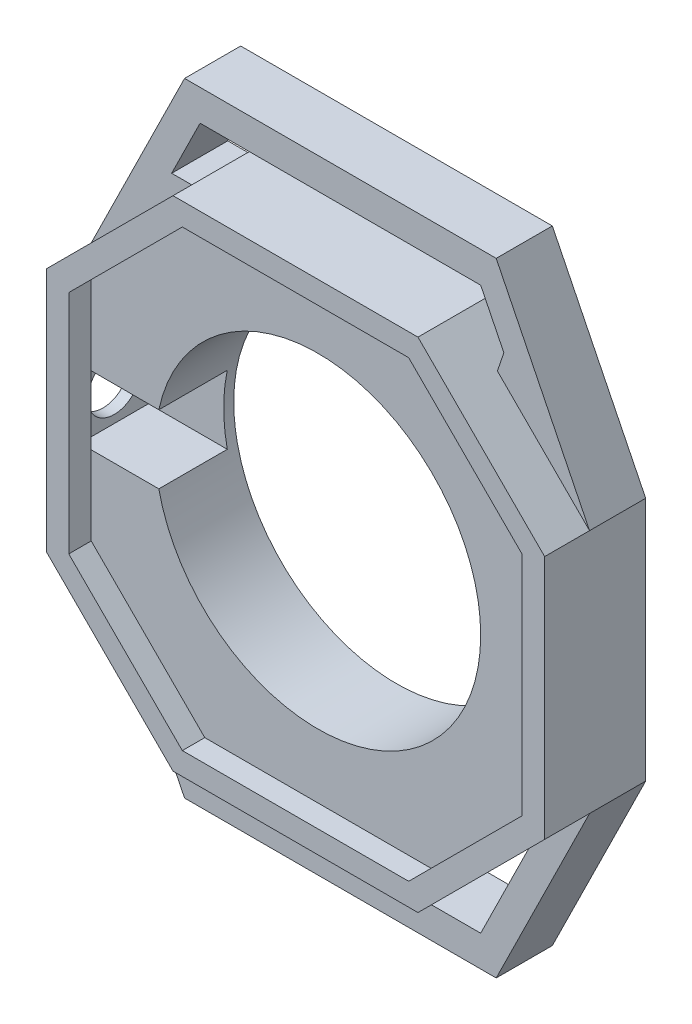
SolidWorks part; units mm, degrees
ref_plane "Front Plane" through (0, 0, 0) normal (0, 0, 1) x (1, 0, 0)
ref_plane "Top Plane" through (0, 0, 0) normal (0, 1, 0) x (1, 0, 0)
ref_plane "Right Plane" through (0, 0, 0) normal (1, 0, 0) x (0, 0, -1)
ref_plane "Plane1" through (0, 0, 0) normal (0, 0, -1) x (-1, 0, 0)
sketch "Sketch1" plane through (0, 0, 0) normal (0, 0, -1) x (-1, 0, 0)
  line L0 (-144.96, -75.66) -> (-164.96, -75.66) construction
  line L1 (-134.96, -85.66) -> (-144.96, -75.66) construction
  line L2 (-134.96, -105.66) -> (-134.96, -85.66) construction
  line L3 (-144.96, -115.66) -> (-134.96, -105.66) construction
  line L4 (-164.96, -115.66) -> (-144.96, -115.66) construction
  line L5 (-174.96, -105.66) -> (-164.96, -115.66) construction
  line L6 (-174.96, -85.66) -> (-174.96, -105.66) construction
  line L7 (-164.96, -75.66) -> (-174.96, -85.66) construction
  line L8 (-144.96, -75.66) -> (-164.96, -75.66) construction
  line L9 (-134.96, -85.66) -> (-144.96, -75.66) construction
  line L10 (-134.96, -105.66) -> (-134.96, -85.66) construction
  line L11 (-144.96, -115.66) -> (-134.96, -105.66) construction
  line L12 (-164.96, -115.66) -> (-144.96, -115.66) construction
  line L13 (-174.96, -105.66) -> (-164.96, -115.66) construction
  line L14 (-174.96, -85.66) -> (-174.96, -105.66) construction
  line L15 (-164.96, -75.66) -> (-174.96, -85.66) construction
  line L16 (-144.8772, -75.46) -> (-165.0428, -75.46)
  line L17 (-165.0428, -75.46) -> (-175.16, -85.5772)
  line L18 (-175.16, -85.5772) -> (-175.16, -105.7428)
  line L19 (-175.16, -105.7428) -> (-165.0428, -115.86)
  line L20 (-165.0428, -115.86) -> (-144.8772, -115.86)
  line L21 (-144.8772, -115.86) -> (-134.76, -105.7428)
  line L22 (-134.76, -105.7428) -> (-134.76, -85.5772)
  line L23 (-134.76, -85.5772) -> (-144.8772, -75.46)
  line L24 (-132.76, -106.5713) -> (-132.76, -84.7487)
  line L25 (-132.76, -84.7487) -> (-144.0487, -73.46)
  line L26 (-144.0487, -73.46) -> (-165.8713, -73.46)
  line L27 (-165.8713, -73.46) -> (-177.16, -84.7487)
  line L28 (-177.16, -84.7487) -> (-177.16, -106.5713)
  line L29 (-177.16, -106.5713) -> (-165.8713, -117.86)
  line L30 (-165.8713, -117.86) -> (-144.0487, -117.86)
  line L31 (-144.0487, -117.86) -> (-132.76, -106.5713)
  circle A0 centre (-154.96, -95.66) radius 13.5 construction
  circle A1 centre (-154.96, -95.66) radius 13.5 construction
  circle A2 centre (-154.96, -95.66) radius 14.5
  dimension "D1" = 1
  dimension "D2" = 0.2
  dimension "D3" = 2
extrude "Boss-Extrude1" add sketch "Sketch1" along normal blind 7 contours A2 | L27 L28 L29 L30 L31 L24 L25 L26 region at (154.96, -95.66, 0)
extrude "Boss-Extrude2" add sketch "Sketch1<3>" against normal blind 2 contours L30 L31 L24 L25 L26 L27 L28 L29 L23 L22 L21 L20 L19 L18 L17 L16 region at (138.8484, -111.7716, 0)
sketch "Sketch1<3>" plane through (0, 0, 0) normal (0, 0, -1) x (-1, 0, 0) same geometry as "Sketch1"
ref_plane "Plane2" through (0, 0, -3.5) normal (0, 0, 1) x (1, 0, 0)
sketch "Sketch2" plane through (0, 0, -7) normal (0, 0, 1) x (1, 0, 0)
  line L0 (142.46, -70.66) -> (167.46, -70.66)
  line L1 (141.078, -70.66) -> (141.078, -67.896) construction
  line L2 (168.842, -70.66) -> (168.842, -67.896) construction
  line L3 (141.078, -67.896) -> (168.842, -67.896)
  line L4 (144.0487, -73.46) -> (165.8713, -73.46) construction
  line L5 (154.96, -73.46) -> (154.96, -68.7069) construction
  line L6 (132.76, -84.7487) -> (141.078, -67.896)
  line L7 (168.842, -70.66) -> (168.842, -73.46) construction
  line L9 (144.0487, -73.46) -> (141.078, -73.46) construction
  line L10 (141.078, -73.46) -> (141.078, -70.66) construction
  line L11 (168.842, -70.66) -> (168.842, -73.46) construction
  line L12 (168.842, -73.46) -> (165.8713, -73.46) construction
  line L13 (177.16, -84.7487) -> (168.842, -67.896)
  line L15 (141.078, -70.66) -> (141.078, -73.46) construction
  line L17 (138.1827, -79.326) -> (132.76, -84.7487)
  line L18 (171.7373, -79.326) -> (177.16, -84.7487)
  line L19 (141.078, -73.46) -> (138.1827, -79.326)
  line L20 (168.842, -73.46) -> (171.7373, -79.326)
  line L21 (144.0487, -73.46) -> (138.1827, -79.326) construction
  line L22 (165.8713, -73.46) -> (171.7373, -79.326) construction
  line L23 (141.078, -73.46) -> (142.46, -70.66)
  line L24 (168.842, -73.46) -> (167.46, -70.66)
  line L25 (141.078, -70.66) -> (142.46, -70.66) construction
  line L26 (167.46, -70.66) -> (168.842, -70.66) construction
  line L27 (154.96, -95.66) -> (141.078, -67.896) construction
  point P22 (0, 0)
  line M19 (165.8713, -73.46) -> (177.16, -84.7487)
  line M25 (132.76, -84.7487) -> (144.0487, -73.46)
  dimension "D2" = 25
extrude "Boss-Extrude3" add sketch "Sketch2" along normal blind 5 contours L13 L12 L7 L0 L10 L9 L6 L3 M19 M25 region at (141.3431, -71.8498, -7)
ref_plane "Plane3" through (0, -95.66, 0) normal (0, -1, 0) x (-1, 0, 0)
chamfer "Chamfer1" distance 5 angle 45 2 edges at (171.7373, -79.326, -4.5) (138.1827, -79.326, -4.5) first distance on face at (169.5986, -74.993, -4.5) first distance on face at (138.3305, -79.1782, -2.3333)
mirror "Mirror1" about plane through (0, -95.66, 0) normal (0, -1, 0) of "Boss-Extrude3"
sketch "Sketch3" plane through (132.76, 0, 0) normal (-1, 0, 0) x (0, 0, 1)
  line L0 (-2, -84.7487) -> (-2, -106.5713) construction
  line L1 (-6.1, -92.61) -> (0, -92.61)
  line L2 (-6.1, -92.61) -> (-6.1, -98.71)
  line L3 (-6.1, -98.71) -> (0, -98.71)
  line L4 (0, -92.61) -> (0, -98.71)
  line L5 (-6.1, -92.61) -> (0, -98.71) construction
  line L6 (-6.1, -98.71) -> (0, -92.61) construction
  line L7 (-2, -95.66) -> (-3.05, -95.66) construction
  line L8 (0, -110.16) -> (0, -81.16) construction
  line L9 (0, -110.16) -> (0, -81.16) construction
  circle A0 centre (-3.05, -95.66) radius 2.35
  point P0 (-3.05, -95.66)
  point P7 (0, 0)
  dimension "D3" = 4.7
  dimension "D1" = 6.1
  dimension "D2" = 6.1
extrude "Cut-Extrude1" cut sketch "Sketch3" against normal up to surface (7.0244 mm away) from offset 1 contours A0 | L4 L1 L2 L3 A0 region at (132.76, -92.6963, -3.05) region at (132.76, -95.66, -3.05) up to face at (140.46, -95.66, -7) offset against normal yes
extrude "Cut-Extrude2" cut sketch "Sketch3<3>" against normal blind 5 contours A0 region at (132.76, -95.66, -3.05)
sketch "Sketch3<3>" plane through (132.76, 0, 0) normal (-1, 0, 0) x (0, 0, 1) same geometry as "Sketch3"
